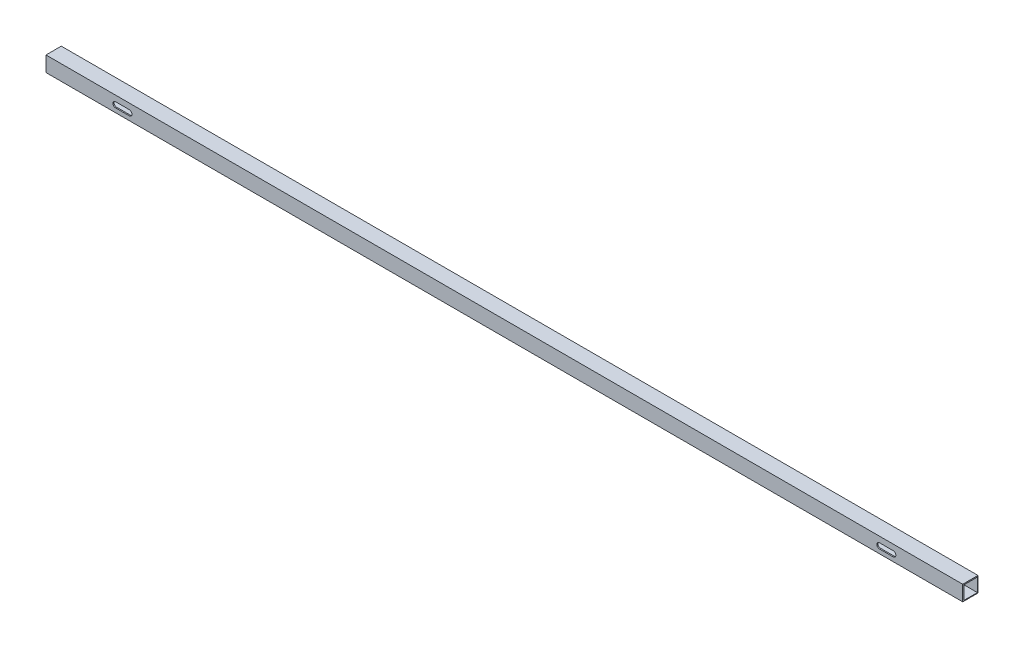
SolidWorks part; units mm, degrees
ref_plane "正面" through (0, 0, 0) normal (0, 0, 1) x (1, 0, 0)
ref_plane "平面" through (0, 0, 0) normal (0, 1, 0) x (1, 0, 0)
ref_plane "右側面" through (0, 0, 0) normal (1, 0, 0) x (0, 0, -1)
sketch "ｽｹｯﾁ1" plane through (0, 0, 0) normal (0, 0, 1) x (1, 0, 0)
  line L1 (0, 0) -> (1200, 0)
  line L2 (0, 0) -> (0, 20)
  line L3 (0, 20) -> (1200, 20)
  line L4 (1200, 0) -> (1200, 20)
  dimension "D1" = 1200
  dimension "D2" = 20
extrude "ﾎﾞｽ - 押し出し1" add sketch "ｽｹｯﾁ1" along normal blind 10 and the other way blind 10
sketch "ｽｹｯﾁ2" plane through (1200, 0, 0) normal (1, 0, 0) x (0, 0, -1)
  line L0 (10, 20) -> (-10, 20) construction
  line L1 (-8.5, 18.5) -> (9.227, 18.5)
  line L2 (-8.5, 18.5) -> (-8.5, 0.9131)
  line L3 (-8.5, 0.9131) -> (9.227, 0.9131)
  line L4 (9.227, 18.5) -> (9.227, 0.9131)
  line L5 (-10, 0) -> (-10, 20) construction
  dimension "D1" = 1.5
  dimension "D2" = 1.5
extrude "ｶｯﾄ - 押し出し1" cut sketch "ｽｹｯﾁ2" against normal through all
sketch "ｽｹｯﾁ3" plane through (0, 0, 10) normal (0, 0, 1) x (1, 0, 0)
  line L0 (91, 9) -> (109, 9) construction
  line L1 (91, 12.5) -> (109, 12.5)
  line L2 (91, 5.5) -> (109, 5.5)
  line L3 (0, 0) -> (1200, 0) construction
  line L5 (0, 20) -> (0, 0) construction
  arc A0 (91, 12.5) -> (91, 5.5) centre (91, 9) ccw
  arc A1 (109, 5.5) -> (109, 12.5) centre (109, 9) ccw
  point P2 (100, 9)
  dimension "D4" = 18
  dimension "D1" = 9
  dimension "D2" = 100
  dimension "D3" = 7
extrude "ｶｯﾄ - 押し出し2" cut sketch "ｽｹｯﾁ3" against normal up to next
sketch "ｽｹｯﾁ4" plane through (0, 0, 10) normal (0, 0, 1) x (1, 0, 0)
  line L0 (1091, 9) -> (1109, 9) construction
  line L1 (1091, 12.5) -> (1109, 12.5)
  line L2 (1091, 5.5) -> (1109, 5.5)
  line L3 (1200, 0) -> (1200, 20) construction
  line L4 (0, 0) -> (1200, 0) construction
  arc A0 (1091, 12.5) -> (1091, 5.5) centre (1091, 9) ccw
  arc A1 (1109, 5.5) -> (1109, 12.5) centre (1109, 9) ccw
  point P2 (1100, 9)
  dimension "D1" = 100
  dimension "D2" = 9
  dimension "D3" = 18
  dimension "D4" = 7
extrude "ｶｯﾄ - 押し出し3" cut sketch "ｽｹｯﾁ4" against normal up to next
sketch "ｽｹｯﾁ5" plane through (0, 0, 0) normal (0, -1, 0) x (1, 0, 0)
  line L1 (1229.0742, 0) -> (-59.5301, 0) construction
  line L2 (600, -28.7097) -> (600, 31.9158) construction
  circle A0 centre (600, 0) radius 6
extrude "ｶｯﾄ - 押し出し4" cut sketch "ｽｹｯﾁ5" against normal up to next
